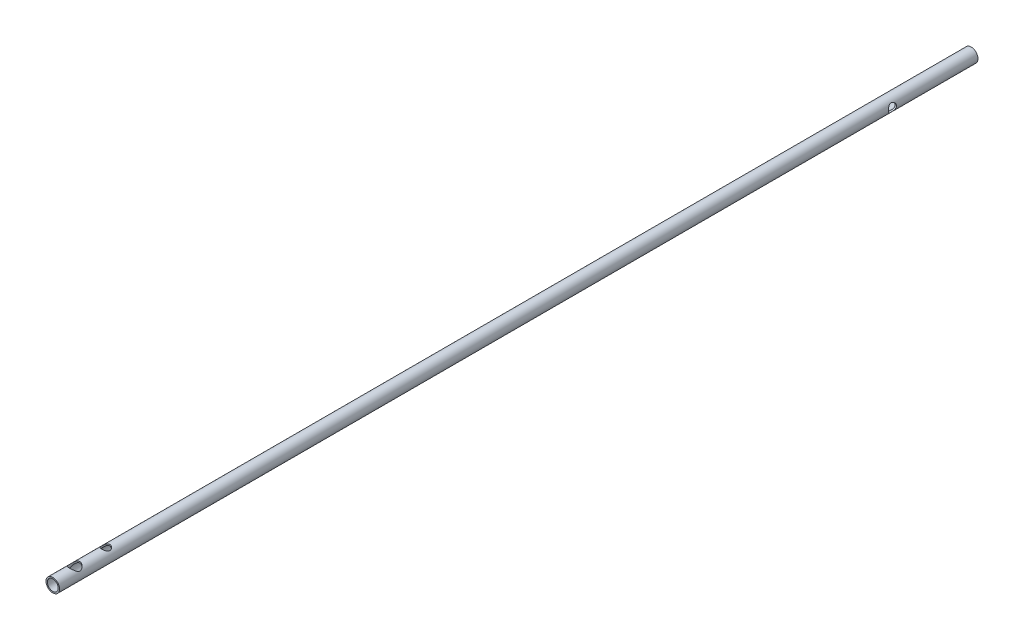
SolidWorks part; units mm, degrees
material "1060 合金"
ref_plane "正面" through (0, 0, 0) normal (0, 0, 1) x (1, 0, 0)
ref_plane "平面" through (0, 0, 0) normal (0, 1, 0) x (1, 0, 0)
ref_plane "右側面" through (0, 0, 0) normal (1, 0, 0) x (0, 0, -1)
sketch "ｽｹｯﾁ1" plane through (0, 0, 0) normal (0, 0, 1) x (1, 0, 0)
  circle A0 centre (0, 0) radius 5
  dimension "D1" = 10
extrude "押し出し-薄板1" add sketch "ｽｹｯﾁ1" along normal blind 676.5 thin thin type one direction reverse wall 1
sketch "ｽｹｯﾁ2" plane through (0, 0, 0) normal (0, 1, 0) x (1, 0, 0)
  line L0 (0, 0) -> (0, 50000) construction
  line L1 (-5, -676.5) -> (5, -676.5) construction
  circle A0 centre (0, -660.5) radius 2
  circle A1 centre (0, -637.5) radius 1.5
  circle A2 centre (0, -660.5) radius 4
  circle A3 centre (0, -637.5) radius 3
  dimension "D1" = 16
  dimension "D2" = 23
  dimension "D3" = 4
  dimension "D4" = 8
  dimension "D5" = 6
  dimension "D6" = 3
extrude "ｶｯﾄ - 押し出し1" cut sketch "ｽｹｯﾁ2" against normal through all both and the other way through all contours L0 A1 | A1 L0 | L0 A0 | A0 L0 region at (0, 0, 660.5) region at (0, 0, 637.5)
extrude "ｶｯﾄ - 押し出し2" cut sketch "ｽｹｯﾁ2<3>" along normal through all contours A2 | A3
sketch "ｽｹｯﾁ2<3>" plane through (0, 0, 0) normal (0, 1, 0) x (1, 0, 0) same geometry as "ｽｹｯﾁ2"
sketch "ｽｹｯﾁ3" plane through (0, 0, 0) normal (1, 0, 0) x (0, 0, -1)
  line L0 (0, 0) -> (50000, 0) construction
  line L1 (0, -5) -> (0, 5) construction
  circle A0 centre (-63, 0) radius 1.5
  circle A1 centre (-63, 0) radius 3
  dimension "D1" = 63
  dimension "D2" = 3
  dimension "D3" = 6
extrude "ｶｯﾄ - 押し出し3" cut sketch "ｽｹｯﾁ3" against normal through all both and the other way through all contours A0
extrude "ｶｯﾄ - 押し出し4" cut sketch "ｽｹｯﾁ3<3>" along normal blind 10 contours A1
sketch "ｽｹｯﾁ3<3>" plane through (0, 0, 0) normal (1, 0, 0) x (0, 0, -1) same geometry as "ｽｹｯﾁ3"
